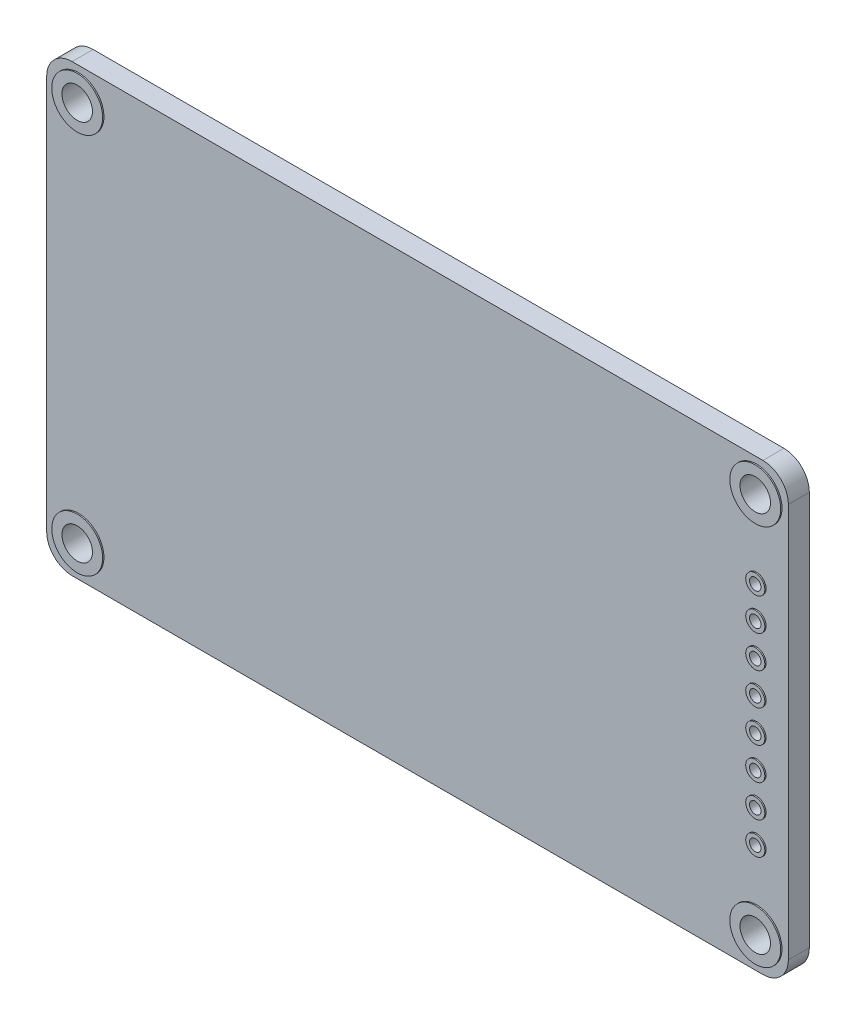
SolidWorks part; units mm, degrees
ref_plane "Спереди" through (0, 0, 0) normal (0, 0, 1) x (1, 0, 0)
ref_plane "Сверху" through (0, 0, 0) normal (0, 1, 0) x (1, 0, 0)
ref_plane "Справа" through (0, 0, 0) normal (1, 0, 0) x (0, 0, -1)
sketch "Эскиз1" plane through (0, 0, 0) normal (0, 0, 1) x (1, 0, 0)
  line L1 (-27.15, -17.5) -> (27.15, -17.5)
  line L2 (-29.15, -15.5) -> (-29.15, 15.5)
  line L3 (-27.15, 17.5) -> (27.15, 17.5)
  line L4 (29.15, -15.5) -> (29.15, 15.5)
  line L5 (-29.15, -17.5) -> (29.15, 17.5) construction
  line L6 (-29.15, 17.5) -> (29.15, -17.5) construction
  arc A0 (-27.15, -17.5) -> (-29.15, -15.5) centre (-27.15, -15.5) cw
  arc A1 (27.15, -17.5) -> (29.15, -15.5) centre (27.15, -15.5) ccw
  arc A2 (27.15, 17.5) -> (29.15, 15.5) centre (27.15, 15.5) cw
  arc A3 (-29.15, 15.5) -> (-27.15, 17.5) centre (-27.15, 15.5) cw
  point P0 (0, 0)
  dimension "D3" = 2
  dimension "D1" = 35
  dimension "D2" = 58.3
extrude "Бобышка-Вытянуть1" add sketch "Эскиз1" along normal blind 1.65
hole_wizard "Отверстие с зазором M21" positions "Эскиз3" profile "Эскиз4" hole size "M2" standard "DIN"
sketch "Эскиз3" plane through (0, 0, 1.65) normal (0, 0, 1) x (1, 0, 0)
  line L1 (-26.65, -15) -> (26.65, -15)
  line L2 (-26.65, -15) -> (-26.65, 15)
  line L3 (-26.65, 15) -> (26.65, 15)
  line L4 (26.65, -15) -> (26.65, 15)
  line L5 (-26.65, -15) -> (26.65, 15) construction
  line L6 (-26.65, 15) -> (26.65, -15) construction
  line L7 (27.15, 17.5) -> (-27.15, 17.5) construction
  line L8 (-29.15, 15.5) -> (-29.15, -15.5) construction
  point P1 (26.65, 15)
  point P154 (-26.65, -15)
  point P155 (-26.65, 15)
  point P156 (26.65, -15)
  dimension "D1" = 2.5
  dimension "D2" = 2.5
sketch "Эскиз4" plane through (26.65, 15, 1.65) normal (1, 0, 0) x (0, -1, 0)
  line L0 (0, 0) -> (0, 10.721)
  line L1 (0, 10.721) -> (1.2, 10)
  line L2 (1.2, 10) -> (1.2, 0)
  line L5 (1.2, 0) -> (0, 0)
  line L10 (0, 10.721) -> (-1.2, 10) construction
  line L11 (0, -6.35) -> (0, 107.95) construction
  dimension "Диаметр отверстия" = 2.4
  dimension "Глубина отверстия" = 10
  dimension "Угол заточки сверла" = 118
sketch "Эскиз5" plane through (0, 0, 1.65) normal (0, 0, 1) x (1, 0, 0)
  line L0 (26.65, 8.89) -> (26.65, -8.89) construction
  line L1 (29.15, -15.5) -> (29.15, 15.5) construction
  circle A0 centre (26.65, -8.89) radius 0.45
  circle A1 centre (26.65, -6.35) radius 0.45
  circle A2 centre (26.65, -3.81) radius 0.45
  circle A3 centre (26.65, -1.27) radius 0.45
  circle A4 centre (26.65, 1.27) radius 0.45
  circle A5 centre (26.65, 3.81) radius 0.45
  circle A6 centre (26.65, 6.35) radius 0.45
  circle A7 centre (26.65, 8.89) radius 0.45
  point P2 (26.65, 0)
  dimension "D1" = 0.9
  dimension "D4" = 2.54
  dimension "D3" = 2.5
  dimension "D2" = 8
extrude "Вырез-Вытянуть1" cut sketch "Эскиз5" against normal through all
sketch "Эскиз6" plane through (0, 0, 1.65) normal (0, 0, 1) x (1, 0, 0)
  circle A0 centre (-26.65, -15) radius 1.2 construction
  circle A1 centre (26.65, -15) radius 1.2 construction
  circle A2 centre (26.65, -8.89) radius 0.45 construction
  circle A3 centre (26.65, -6.35) radius 0.45 construction
  circle A4 centre (26.65, -3.81) radius 0.45 construction
  circle A5 centre (26.65, -1.27) radius 0.45 construction
  circle A6 centre (26.65, 1.27) radius 0.45 construction
  circle A7 centre (26.65, 3.81) radius 0.45 construction
  circle A8 centre (26.65, 6.35) radius 0.45 construction
  circle A9 centre (26.65, 8.89) radius 0.45 construction
  circle A10 centre (26.65, 15) radius 1.2 construction
  circle A11 centre (-26.65, 15) radius 1.2 construction
  circle A12 centre (-26.65, -15) radius 1.2
  circle A13 centre (26.65, -15) radius 1.2
  circle A14 centre (26.65, -8.89) radius 0.45
  circle A15 centre (26.65, -6.35) radius 0.45
  circle A16 centre (26.65, -3.81) radius 0.45
  circle A17 centre (26.65, -1.27) radius 0.45
  circle A18 centre (26.65, 1.27) radius 0.45
  circle A19 centre (26.65, 3.81) radius 0.45
  circle A20 centre (26.65, 6.35) radius 0.45
  circle A21 centre (26.65, 8.89) radius 0.45
  circle A22 centre (26.65, 15) radius 1.2
  circle A23 centre (-26.65, 15) radius 1.2
  circle A24 centre (-26.65, 15) radius 2
  circle A25 centre (26.65, 15) radius 2
  circle A26 centre (26.65, -15) radius 2
  circle A27 centre (-26.65, -15) radius 2
  circle A28 centre (26.65, -8.89) radius 0.75
  circle A29 centre (26.65, -6.35) radius 0.75
  circle A30 centre (26.65, -3.81) radius 0.75
  circle A31 centre (26.65, -1.27) radius 0.75
  circle A32 centre (26.65, 1.27) radius 0.75
  circle A33 centre (26.65, 3.81) radius 0.75
  circle A34 centre (26.65, 6.35) radius 0.75
  circle A35 centre (26.65, 8.89) radius 0.75
  dimension "D1" = 0.8
  dimension "D2" = 0.3
extrude "Бобышка-Вытянуть2" add sketch "Эскиз6" along normal blind 0.1 and the other way offset from surface (1.75 mm away) 0.1 other way up to face at (27.1, -8.89, 0)
sketch "Эскиз7" plane through (0, 0, 0) normal (0, 0, -1) x (-1, 0, 0)
  line L0 (18.45, -4.55) -> (18.45, -5.45)
  line L1 (15.95, -6.55) -> (18.45, -6.55)
  line L2 (15.95, -6.55) -> (15.95, -7.45)
  line L3 (15.95, -7.45) -> (18.45, -7.45)
  line L4 (18.45, -6.55) -> (18.45, -7.45)
  line L5 (15.95, -6.55) -> (18.45, -7.45) construction
  line L6 (15.95, -7.45) -> (18.45, -6.55) construction
  line L7 (15.95, -5.45) -> (18.45, -5.45)
  line L8 (15.95, -4.55) -> (18.45, -5.45) construction
  line L9 (15.95, -5.45) -> (18.45, -4.55) construction
  line L10 (15.95, -4.55) -> (15.95, -5.45)
  line L11 (15.95, -4.55) -> (18.45, -4.55)
  line L12 (18.45, -2.55) -> (18.45, -3.45)
  line L13 (15.95, -3.45) -> (18.45, -3.45)
  line L14 (15.95, -2.55) -> (18.45, -3.45) construction
  line L15 (15.95, -3.45) -> (18.45, -2.55) construction
  line L16 (15.95, -2.55) -> (15.95, -3.45)
  line L17 (15.95, -2.55) -> (18.45, -2.55)
  line L18 (18.45, -0.55) -> (18.45, -1.45)
  line L19 (15.95, -1.45) -> (18.45, -1.45)
  line L20 (15.95, -0.55) -> (18.45, -1.45) construction
  line L21 (15.95, -1.45) -> (18.45, -0.55) construction
  line L22 (15.95, -0.55) -> (15.95, -1.45)
  line L23 (15.95, -0.55) -> (18.45, -0.55)
  line L24 (18.45, 1.45) -> (18.45, 0.55)
  line L25 (15.95, 0.55) -> (18.45, 0.55)
  line L26 (15.95, 1.45) -> (18.45, 0.55) construction
  line L27 (15.95, 0.55) -> (18.45, 1.45) construction
  line L28 (15.95, 1.45) -> (15.95, 0.55)
  line L29 (15.95, 1.45) -> (18.45, 1.45)
  line L30 (18.45, 3.45) -> (18.45, 2.55)
  line L31 (15.95, 2.55) -> (18.45, 2.55)
  line L32 (15.95, 3.45) -> (18.45, 2.55) construction
  line L33 (15.95, 2.55) -> (18.45, 3.45) construction
  line L34 (15.95, 3.45) -> (15.95, 2.55)
  line L35 (15.95, 3.45) -> (18.45, 3.45)
  line L36 (18.45, 5.45) -> (18.45, 4.55)
  line L37 (15.95, 4.55) -> (18.45, 4.55)
  line L38 (15.95, 5.45) -> (18.45, 4.55) construction
  line L39 (15.95, 4.55) -> (18.45, 5.45) construction
  line L40 (15.95, 5.45) -> (15.95, 4.55)
  line L41 (15.95, 5.45) -> (18.45, 5.45)
  line L42 (18.45, 7.45) -> (18.45, 6.55)
  line L43 (15.95, 6.55) -> (18.45, 6.55)
  line L44 (15.95, 7.45) -> (18.45, 6.55) construction
  line L45 (15.95, 6.55) -> (18.45, 7.45) construction
  line L46 (15.95, 7.45) -> (15.95, 6.55)
  line L47 (15.95, 7.45) -> (18.45, 7.45)
  line L48 (17.2, 7) -> (17.2, -7) construction
  line L49 (29.15, 15.5) -> (29.15, -15.5) construction
  line L50 (23.2, 9.65) -> (23.2, -9.65) construction
  line L51 (21.45, -8.75) -> (24.95, -8.75)
  line L52 (21.45, -8.75) -> (21.45, -10.55)
  line L53 (21.45, -10.55) -> (24.95, -10.55)
  line L54 (24.95, -8.75) -> (24.95, -10.55)
  line L55 (21.45, -8.75) -> (24.95, -10.55) construction
  line L56 (21.45, -10.55) -> (24.95, -8.75) construction
  line L57 (21.45, 8.75) -> (24.95, 8.75)
  line L58 (21.45, 8.75) -> (21.45, 10.55)
  line L59 (21.45, 10.55) -> (24.95, 10.55)
  line L60 (24.95, 8.75) -> (24.95, 10.55)
  line L61 (21.45, 8.75) -> (24.95, 10.55) construction
  line L62 (21.45, 10.55) -> (24.95, 8.75) construction
  point P0 (17.2, -7)
  point P35 (17.2, 0)
  point P39 (23.2, -9.65)
  point P44 (23.2, 9.65)
  point P52 (23.2, 0)
  dimension "D1" = 0.9
  dimension "D2" = 2.5
  dimension "D4" = 2
  dimension "D5" = 11.95
  dimension "D6" = 1.8
  dimension "D7" = 3.5
  dimension "D8" = 5.95
  dimension "D9" = 19.3
  dimension "D3" = 8
extrude "Бобышка-Вытянуть3" add sketch "Эскиз7" along normal blind 0.1
